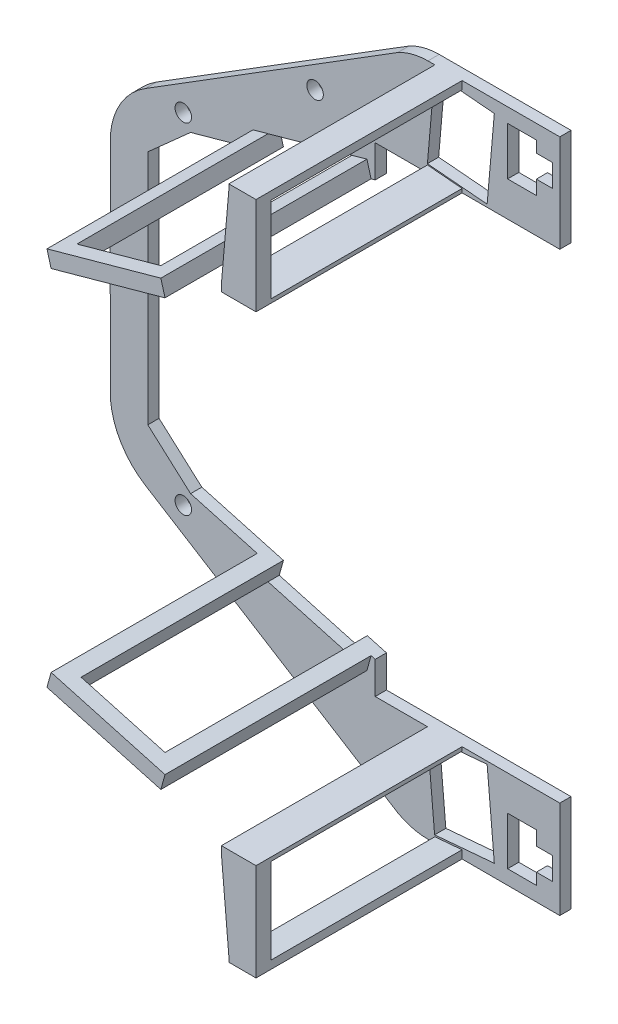
SolidWorks part; units mm, degrees
ref_plane "Front Plane" through (0, 0, 0) normal (0, 0, 1) x (1, 0, 0)
ref_plane "Top Plane" through (0, 0, 0) normal (0, 1, 0) x (1, 0, 0)
ref_plane "Right Plane" through (0, 0, 0) normal (1, 0, 0) x (0, 0, -1)
sketch "Sketch1" plane through (0, 0, 0) normal (0, 0, 1) x (1, 0, 0)
  line L0 (65, 15) -> (65, 5)
  line L1 (65, 5) -> (47.403, 5.0215)
  line L2 (46.938, 5.043) -> (47.868, 5) construction
  line L3 (43.379, 6.064) -> (9.7, 27.063)
  line L4 (5.042, 34.624) -> (5, 50)
  line L5 (65, 15) -> (65, 18)
  line L6 (65, 85) -> (65, 15) construction
  line L7 (65, 18) -> (40.3675, 18)
  line L8 (40.3675, 18) -> (40.3675, 22.2992)
  line L9 (40.3675, 22.2992) -> (37.8165, 23.0061)
  line L10 (10.021, 34.227) -> (10.021, 65.773)
  line L11 (65, 50) -> (5, 50) construction
  line L13 (65, 50) -> (10.021, 50) construction
  line L14 (65, 82) -> (40.3675, 82)
  line L15 (65, 85) -> (65, 82)
  line L16 (65, 85) -> (65, 95)
  line L17 (65, 95) -> (47.403, 94.9785)
  line L18 (40.3675, 82) -> (40.3675, 77.7008)
  line L19 (40.3675, 77.7008) -> (37.8165, 76.9939)
  line L20 (43.379, 93.936) -> (9.7, 72.937)
  line L21 (5.042, 65.376) -> (5, 50)
  line L22 (26.6181, 73.8907) -> (26.0635, 75.892)
  line L23 (26.0635, 75.892) -> (37.2619, 78.9952)
  line L24 (37.2619, 78.9952) -> (37.8165, 76.9939)
  line L27 (47.3336, 83.0656) -> (55.3032, 82.3683)
  line L28 (55.3032, 82.3683) -> (56.2619, 93.3265)
  line L29 (56.2619, 93.3265) -> (48.2923, 94.0237)
  line L30 (48.2923, 94.0237) -> (47.3336, 83.0656)
  line L31 (58.0329, 86.6518) -> (61.8647, 86.6518)
  line L32 (61.8647, 86.6518) -> (61.8647, 88.5446)
  line L33 (61.8647, 88.5446) -> (64.0046, 88.5446)
  line L34 (64.0046, 88.5446) -> (64.0046, 91.5464)
  line L35 (64.0046, 91.5464) -> (61.8649, 91.5464)
  line L39 (10.021, 65.773) -> (15.7286, 70.873)
  line L40 (61.8649, 91.5464) -> (61.8649, 93.072)
  line L41 (61.8649, 93.072) -> (58.0329, 93.072)
  line L42 (58.0329, 93.072) -> (58.0329, 86.6518)
  line L43 (56.2619, 6.6735) -> (48.2923, 5.9763)
  line L44 (55.3032, 17.6317) -> (56.2619, 6.6735)
  line L45 (47.3336, 16.9344) -> (55.3032, 17.6317)
  line L46 (48.2923, 5.9763) -> (47.3336, 16.9344)
  line L47 (37.2619, 21.0048) -> (37.8165, 23.0061)
  line L48 (26.6181, 26.1093) -> (26.0635, 24.108)
  line L49 (26.0635, 24.108) -> (37.2619, 21.0048)
  line L50 (58.0329, 13.3482) -> (61.8647, 13.3482)
  line L51 (61.8647, 13.3482) -> (61.8647, 11.4554)
  line L52 (61.8647, 11.4554) -> (64.0046, 11.4554)
  line L53 (64.0046, 11.4554) -> (64.0046, 8.4536)
  line L54 (64.0046, 8.4536) -> (61.8649, 8.4536)
  line L55 (61.8649, 8.4536) -> (61.8649, 6.928)
  line L56 (61.8649, 6.928) -> (58.0329, 6.928)
  line L57 (58.0329, 6.928) -> (58.0329, 13.3482)
  line L58 (26.6181, 73.8907) -> (15.7286, 70.873)
  line L59 (26.6181, 26.1093) -> (15.7286, 29.127)
  line L60 (10.021, 34.227) -> (15.7286, 29.127)
  arc A0 (47.403, 5.0215) -> (43.379, 6.064) centre (47.4132, 13.3482) cw
  arc A1 (9.7, 27.063) -> (5.042, 34.624) centre (14.9798, 35.5309) cw
  circle A2 centre (14.76, 27.32) radius 1.1 construction
  arc A3 (47.403, 94.9785) -> (43.379, 93.936) centre (47.4132, 86.6518) ccw
  arc A4 (9.7, 72.937) -> (5.042, 65.376) centre (14.9798, 64.4691) ccw
  circle A5 centre (32.343, 84.089) radius 1.1
  circle A6 centre (14.76, 72.68) radius 1.1
  circle A7 centre (14.76, 27.32) radius 1.1
  circle A8 centre (32.343, 15.911) radius 1.1
  point P15 (5.021, 42.312)
  point P44 (10.021, 50)
  dimension "D2" = 5
  dimension "D3" = 2
  dimension "D1" = 3
extrude "Boss-Extrude1" add sketch "Sketch1" along normal blind 1.5
sketch "Sketch2" plane through (0, 0, 1.5) normal (0, 0, 1) x (1, 0, 0)
  line L0 (26.6181, 26.1093) -> (26.0635, 24.108)
  line L3 (26.6181, 26.1093) -> (15.7286, 29.127) construction
  line L4 (24.6181, 26.6636) -> (26.6181, 26.1093)
  line L5 (26.0635, 24.108) -> (24.0635, 24.6622)
  line L6 (24.0635, 24.6622) -> (24.6181, 26.6636)
  line L7 (37.2619, 21.0048) -> (37.8165, 23.0061)
  line L12 (37.8165, 23.0061) -> (39.8165, 22.4519)
  line L13 (40.3675, 22.2992) -> (37.8165, 23.0061) construction
  line L14 (39.8165, 22.4519) -> (39.2619, 20.4506)
  line L15 (39.2619, 20.4506) -> (37.2619, 21.0048)
  line L16 (5, 50) -> (65, 50) construction
  line L18 (65, 85) -> (65, 15) construction
  line L19 (39.8165, 77.5481) -> (39.2619, 79.5494)
  line L20 (37.8165, 76.9939) -> (39.8165, 77.5481)
  line L21 (37.2619, 78.9952) -> (37.8165, 76.9939)
  line L22 (39.2619, 79.5494) -> (37.2619, 78.9952)
  line L23 (26.0635, 75.892) -> (24.0635, 75.3378)
  line L24 (26.6181, 73.8907) -> (26.0635, 75.892)
  line L25 (24.6181, 73.3364) -> (26.6181, 73.8907)
  line L26 (24.0635, 75.3378) -> (24.6181, 73.3364)
  line L27 (47.3403, 18) -> (51.9624, 18)
  line L28 (65, 18) -> (40.3675, 18) construction
  line L31 (47.3403, 18) -> (47.3403, 17.0838)
  line L32 (47.3403, 17.0838) -> (51.9624, 17.4882)
  line L33 (51.9624, 17.4882) -> (51.9624, 18)
  line L34 (48.3302, 5.77) -> (51.9624, 6.0878)
  line L35 (51.9624, 6.0878) -> (51.9624, 5.0159)
  line L36 (47.403, 5.0215) -> (65, 5) construction
  line L37 (51.9624, 5.0159) -> (48.3302, 5.0204)
  line L38 (48.3302, 5.0204) -> (48.3302, 5.5519)
  line L39 (48.3302, 5.5519) -> (48.3302, 5.77)
  line L40 (48.3302, 94.9796) -> (48.3302, 94.4481)
  line L41 (51.9624, 94.9841) -> (48.3302, 94.9796)
  line L42 (51.9624, 93.9122) -> (51.9624, 94.9841)
  line L43 (48.3302, 94.23) -> (51.9624, 93.9122)
  line L44 (48.3302, 94.4481) -> (48.3302, 94.23)
  line L45 (47.3403, 82.9162) -> (51.9624, 82.5118)
  line L46 (47.3403, 82) -> (47.3403, 82.9162)
  line L47 (47.3403, 82) -> (51.9624, 82)
  line L48 (51.9624, 82.5118) -> (51.9624, 82)
  dimension "D1" = 2
  dimension "D2" = 2
extrude "Boss-Extrude2" add sketch "Sketch2" along normal blind 25.5
sketch "Sketch4" plane through (0, 0, 27) normal (0, 0, 1) x (1, 0, 0)
  line L0 (48.3302, 5.0204) -> (48.3302, 5.77)
  line L1 (48.3302, 5.77) -> (47.3403, 17.0838)
  line L2 (47.3403, 17.0838) -> (47.3403, 18)
  line L3 (47.3403, 18) -> (51.9624, 18)
  line L4 (51.9624, 18) -> (51.9624, 17.4882)
  line L5 (51.9624, 17.4882) -> (51.9624, 5.0159)
  line L6 (51.9624, 5.0159) -> (48.3302, 5.0204)
  line L7 (24.6181, 26.6636) -> (39.8165, 22.4519)
  line L8 (39.8165, 22.4519) -> (39.2619, 20.4506)
  line L9 (39.2619, 20.4506) -> (24.0635, 24.6622)
  line L10 (24.0635, 24.6622) -> (24.6181, 26.6636)
  line L11 (5, 50) -> (65, 50) construction
  line L12 (51.9624, 82.5118) -> (51.9624, 94.9841)
  line L13 (51.9624, 82) -> (51.9624, 82.5118)
  line L14 (47.3403, 82) -> (51.9624, 82)
  line L15 (47.3403, 82.9162) -> (47.3403, 82)
  line L16 (48.3302, 94.23) -> (47.3403, 82.9162)
  line L17 (48.3302, 94.9796) -> (48.3302, 94.23)
  line L18 (51.9624, 94.9841) -> (48.3302, 94.9796)
  line L19 (39.2619, 79.5494) -> (24.0635, 75.3378)
  line L20 (39.8165, 77.5481) -> (39.2619, 79.5494)
  line L21 (24.6181, 73.3364) -> (39.8165, 77.5481)
  line L22 (24.0635, 75.3378) -> (24.6181, 73.3364)
extrude "Boss-Extrude4" add sketch "Sketch4" along normal blind 2
